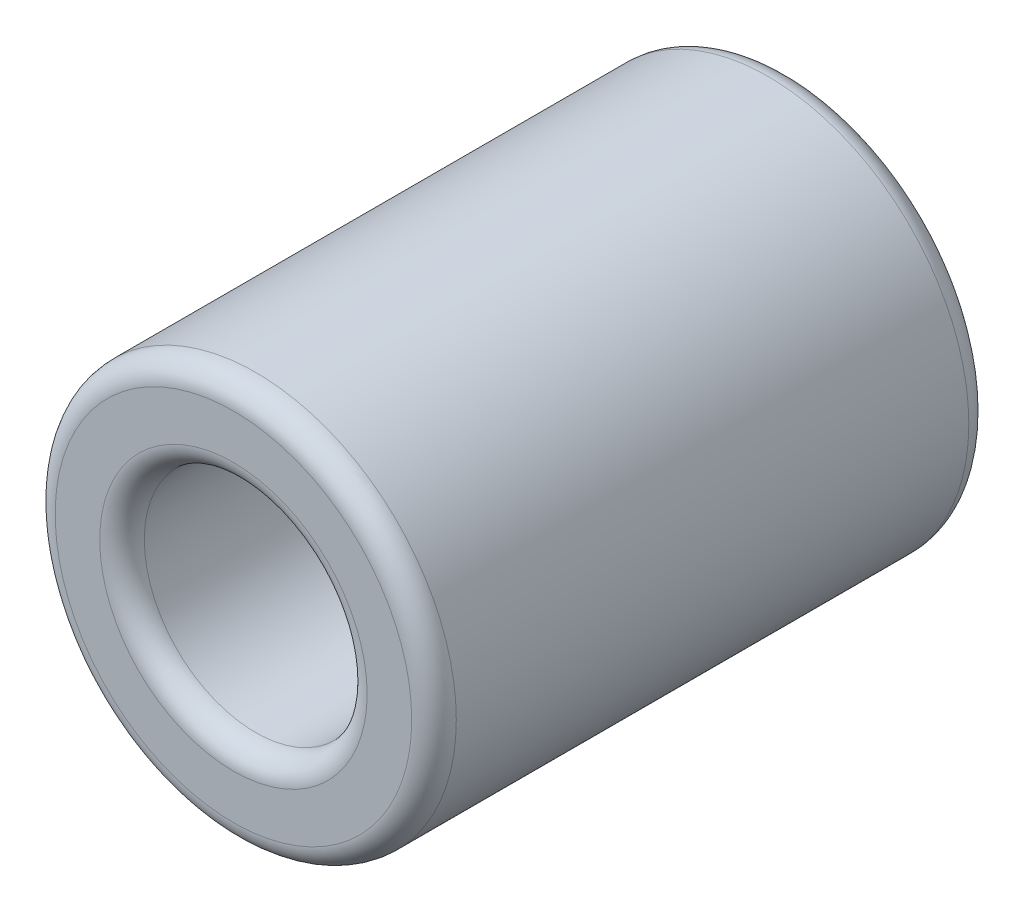
SolidWorks part; units mm, degrees
ref_plane "Front" through (0, 0, 0) normal (0, 0, 1) x (1, 0, 0)
ref_plane "Top" through (0, 0, 0) normal (0, 1, 0) x (1, 0, 0)
ref_plane "Right" through (0, 0, 0) normal (1, 0, 0) x (0, 0, -1)
sketch "Szkic1" plane through (0, 0, 0) normal (0, 0, 1) x (1, 0, 0)
  circle A0 centre (0, 0) radius 5
  circle A1 centre (0, 0) radius 9
  dimension "D1" = 18
  dimension "D2" = 10
extrude "Dodanie-wyciągnięcie1" add sketch "Szkic1" along normal blind 25
fillet "Zaokrąglenie1" radius 1 4 edges at (5, 0, 0) (9, 0, 0) (5, 0, 25) (9, 0, 25)
